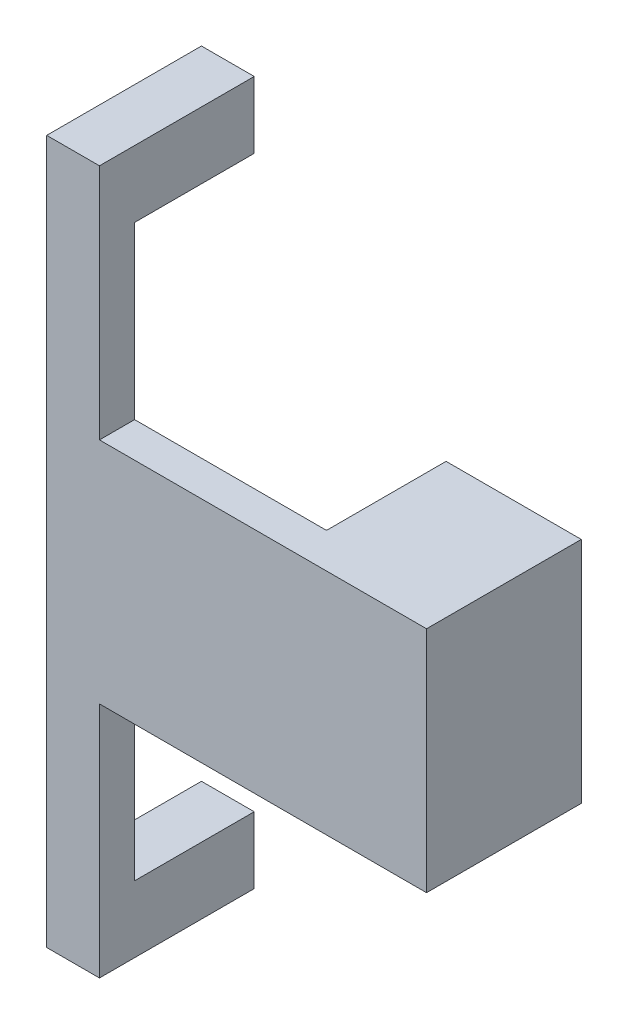
SolidWorks part; units mm, degrees
ref_plane "正面" through (0, 0, 0) normal (0, 0, 1) x (1, 0, 0)
ref_plane "平面" through (0, 0, 0) normal (0, 1, 0) x (1, 0, 0)
ref_plane "右側面" through (0, 0, 0) normal (1, 0, 0) x (0, 0, -1)
sketch "ｽｹｯﾁ1" plane through (0, 0, 0) normal (0, 0, 1) x (1, 0, 0)
  line L6 (10.9106, 0) -> (18.6, 0)
  line L7 (10.9106, -13) -> (18.6, -13)
  line L8 (0, 13.5) -> (0, 9.7115)
  line L9 (-3, 9.7115) -> (-3, 13.5)
  line L10 (-3, -22.7115) -> (0, -22.7115)
  line L11 (-3, -26.5) -> (0, -26.5)
  line L12 (-3, 13.5) -> (0, 13.5)
  line L13 (-3, 9.7115) -> (0, 9.7115)
  line L14 (-3, -5.1) -> (-3, -7.9) construction
  line L15 (-3, -6.5) -> (-10.421, -6.5) construction
  line L16 (-3, -22.7115) -> (-3, -26.5)
  line L17 (0, -26.5) -> (0, -22.7115)
  line L18 (10.9106, 0) -> (10.9106, -13)
  line L19 (18.6, 0) -> (18.6, -13)
extrude "ﾎﾞｽ - 押し出し1" add sketch "ｽｹｯﾁ1" against normal blind 8.8
sketch "ｽｹｯﾁ2" plane through (0, 0, 0) normal (0, 0, 1) x (1, 0, 0)
  line L0 (0, -13) -> (18.6, -13) construction
  line L1 (0, 0) -> (18.6, 0) construction
  line L2 (0, -13) -> (0, -33.8) construction
  line L3 (-3, -26.5) -> (0, -26.5) construction
  line L4 (-3, -7.9) -> (-3, -26.5) construction
  line L5 (-3, -5.1) -> (-3, 13.5) construction
  line L6 (0, 0) -> (0, 20.8) construction
  line L7 (0, 13.5) -> (-3, 13.5) construction
  line L8 (18.6, -13) -> (18.6, 0) construction
  line L9 (0, -13) -> (18.6, -13)
  line L10 (0, 0) -> (18.6, 0)
  line L11 (0, -13) -> (0, -26.5)
  line L12 (-3, -26.5) -> (0, -26.5)
  line L13 (-3, -7.9) -> (-3, -26.5)
  line L14 (-3, -5.1) -> (-3, 13.5)
  line L15 (0, 0) -> (0, 13.5)
  line L16 (0, 13.5) -> (-3, 13.5)
  line L17 (18.6, -13) -> (18.6, 0)
  line L18 (-3, -7.9) -> (-3, -5.1)
extrude "ﾎﾞｽ - 押し出し2" add sketch "ｽｹｯﾁ2" against normal blind 2
